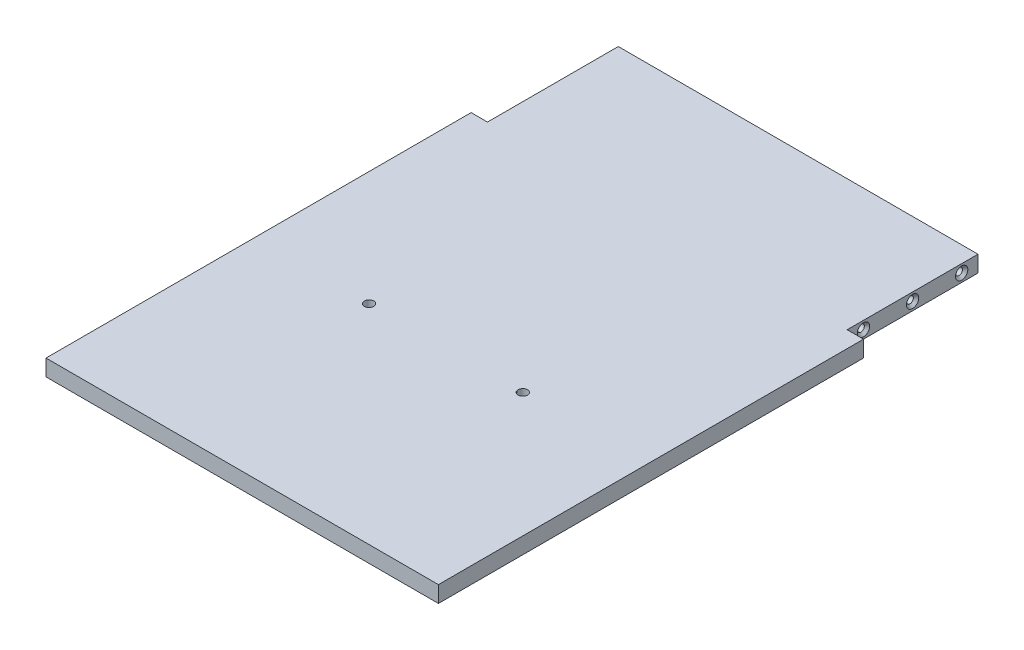
SolidWorks part; units mm, degrees
ref_plane "Front Plane" through (0, 0, 0) normal (0, 0, 1) x (1, 0, 0)
ref_plane "Top Plane" through (0, 0, 0) normal (0, 1, 0) x (1, 0, 0)
ref_plane "Right Plane" through (0, 0, 0) normal (1, 0, 0) x (0, 0, -1)
sketch "Sketch1" plane through (0, 0, 0) normal (0, 1, 0) x (1, 0, 0)
  line L0 (-6.35, 0) -> (-6.35, -50.8)
  line L1 (-6.35, 0) -> (-146.05, 0)
  line L2 (0, -50.8) -> (0, -215.9)
  line L3 (0, -215.9) -> (-152.4, -215.9)
  line L4 (-152.4, -50.8) -> (-152.4, -215.9)
  line L5 (-6.35, -50.8) -> (0, -50.8)
  line L6 (-146.05, 0) -> (-146.05, -50.8)
  line L7 (-146.05, -50.8) -> (-152.4, -50.8)
  point P7 (-3.175, -50.8)
  dimension "D1" = 152.4
  dimension "D2" = 215.9
  dimension "D3" = 50.8
  dimension "D4" = 6.35
  dimension "D5" = 6.35
  dimension "D6" = 50.8
extrude "Boss-Extrude1" add sketch "Sketch1" along normal blind 6.35
sketch "Sketch2" plane through (-6.35, 0, 0) normal (1, 0, 0) x (0, 0, -1)
  line L0 (-50.8, 6.35) -> (-50.8, 0) construction
  line L1 (-50.8, 6.35) -> (-50.8, 0) construction
  line L2 (-50.8, 0) -> (0, 0) construction
  circle A0 centre (-44.45, 3.175) radius 1.8288
  circle A1 centre (-25.4, 3.175) radius 1.8288
  circle A2 centre (-6.35, 3.175) radius 1.8288
  dimension "D4" = 3.175
  dimension "D5" = 3.175
  dimension "D6" = 3.6576
  dimension "D7" = 3.6576
  dimension "D8" = 3.6576
  dimension "D1" = 6.35
  dimension "D2" = 25.4
  dimension "D3" = 44.45
hole_wizard "#6-32 Tapped Hole1" positions "Sketch3" profile "Sketch4" tap size "#6-32" standard "ANSI Inch"
sketch "Sketch3" plane through (-6.35, 0, 0) normal (1, 0, 0) x (0, 0, -1)
  point P0 (-44.45, 3.175)
  point P3 (-25.4, 3.175)
  point P6 (-6.35, 3.175)
sketch "Sketch4" plane through (-6.35, 3.175, 44.45) normal (0, 1, 0) x (0, 0, -1)
  line L0 (0, 0) -> (0, 12.7)
  line L1 (0, 12.7) -> (1.3525, 11.8873)
  line L2 (1.3525, 11.8873) -> (1.3525, 1.0351)
  line L3 (1.3525, 1.0351) -> (2.3876, 0)
  line L5 (2.3876, 0) -> (0, 0)
  line L6 (-1.3525, 1.0351) -> (-2.3876, 0) construction
  line L10 (0, 12.7) -> (-1.3526, 11.8873) construction
  line L11 (0, -6.35) -> (0, 107.95) construction
  dimension "Tap Drill Dia." = 2.7051
  dimension "Tap Drill Depth" = 12.7
  dimension "Near C'Sink Dia." = 4.7752
  dimension "Near C'Sink Angle" = 90
  dimension "Drill Angle" = 118
cosmetic thread "Hole Thread1" parameters "D1"=10.16, "D2"=3.5052
cosmetic thread "Hole Thread2" parameters "D1"=10.16, "D2"=3.5052
cosmetic thread "Hole Thread3" parameters "D1"=10.16, "D2"=3.5052
sketch "Sketch5" plane through (-146.05, 0, 0) normal (-1, 0, 0) x (0, 0, 1)
  circle A0 centre (6.35, 3.175) radius 1.8288
  circle A1 centre (25.4, 3.175) radius 1.8288
  circle A2 centre (44.45, 3.175) radius 1.8288
  dimension "D1" = 3.6576
  dimension "D2" = 3.6576
  dimension "D3" = 3.6576
hole_wizard "#6-32 Tapped Hole2" positions "Sketch6" profile "Sketch7" tap size "#6-32" standard "ANSI Inch"
sketch "Sketch6" plane through (-146.05, 0, 0) normal (-1, 0, 0) x (0, 0, 1)
  point P0 (6.35, 3.175)
  point P3 (25.4, 3.175)
  point P6 (44.45, 3.175)
sketch "Sketch7" plane through (-146.05, 3.175, 6.35) normal (0, 1, 0) x (0, 0, 1)
  line L0 (0, 0) -> (0, 12.7)
  line L1 (0, 12.7) -> (1.3525, 11.8873)
  line L2 (1.3525, 11.8873) -> (1.3525, 1.0351)
  line L3 (1.3525, 1.0351) -> (2.3876, 0)
  line L5 (2.3876, 0) -> (0, 0)
  line L6 (-1.3525, 1.0351) -> (-2.3876, 0) construction
  line L10 (0, 12.7) -> (-1.3526, 11.8873) construction
  line L11 (0, -6.35) -> (0, 107.95) construction
  dimension "Tap Drill Dia." = 2.7051
  dimension "Tap Drill Depth" = 12.7
  dimension "Near C'Sink Dia." = 4.7752
  dimension "Near C'Sink Angle" = 90
  dimension "Drill Angle" = 118
cosmetic thread "Hole Thread4" parameters "D1"=10.16, "D2"=3.5052
cosmetic thread "Hole Thread5" parameters "D1"=10.16, "D2"=3.5052
cosmetic thread "Hole Thread6" parameters "D1"=10.16, "D2"=3.5052
sketch "Sketch8" plane through (0, 6.35, 0) normal (0, 1, 0) x (1, 0, 0)
  line L0 (0, -215.9) -> (0, -50.8) construction
  line L1 (-152.4, -215.9) -> (0, -215.9) construction
  circle A0 centre (-48.26, -134.874) radius 1.8288
  circle A1 centre (-107.95, -134.874) radius 1.8288
  dimension "D1" = 48.26
  dimension "D2" = 81.026
  dimension "D3" = 59.69
  dimension "D4" = 81.026
  dimension "D5" = 3.6576
  dimension "D6" = 3.6576
extrude "Cut-Extrude1" cut sketch "Sketch8" against normal through all
